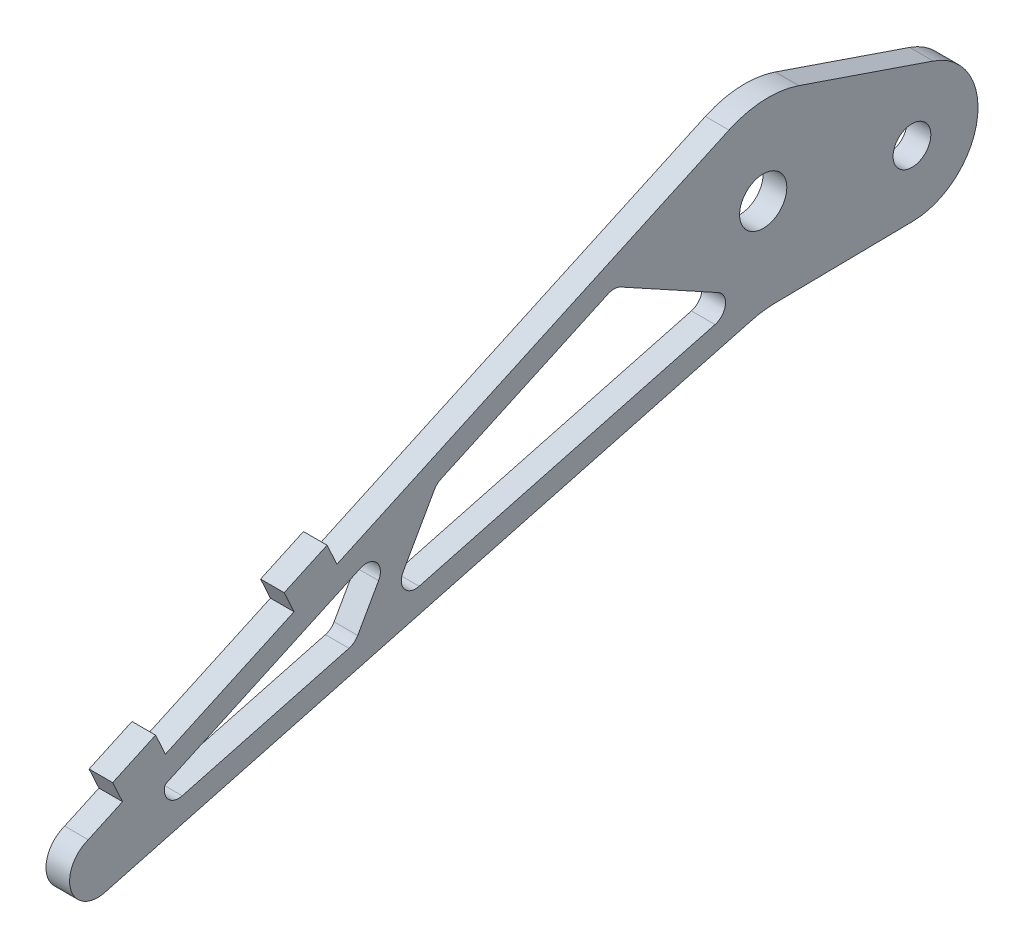
SolidWorks part; units mm, degrees
ref_plane "Front Plane" through (0, 0, 0) normal (1, 0, 0) x (0, 1, 0)
ref_plane "Top Plane" through (0, 0, 0) normal (0, 0, 1) x (0, 1, 0)
ref_plane "Right Plane" through (0, 0, 0) normal (0, 1, 0) x (-1, 0, 0)
sketch "Sketch1" plane through (0, 0, 0) normal (1, 0, 0) x (0, 1, 0)
  line L0 (0, 0) -> (5.5567, 31.5138) construction
  line L1 (5.5567, 31.5138) -> (-45.7463, 172.4677) construction
  line L2 (0, 0) -> (50000, 0) construction
  line L3 (5.5567, 31.5138) -> (-14.4433, 31.5138) construction
  line L4 (-13.9986, -0.1963) -> (-14.4433, 31.5138)
  line L5 (-14.4433, 31.5138) -> (-51.3844, 170.4156)
  line L6 (-45.7463, 172.4677) -> (-51.3844, 170.4156) construction
  line L7 (5.5567, 31.5138) -> (25.5567, 31.5138) construction
  line L8 (13.2486, -4.5247) -> (25.5567, 31.5138)
  line L9 (-45.7463, 172.4677) -> (-40.1081, 174.5199) construction
  line L10 (-40.1081, 174.5199) -> (25.5567, 31.5138)
  line L11 (0, 0) -> (-45.7463, 172.4677) construction
  line L12 (-30.4865, 111.2917) -> (-10.0592, 34.4834)
  line L13 (5.6, 62.9939) -> (-11.7181, 100.7094)
  line L14 (-11.7181, 100.7094) -> (-30.4865, 111.2917)
  line L17 (-15.2745, 108.4546) -> (-38.215, 158.4149)
  line L18 (-38.215, 158.4149) -> (-44.1163, 162.5408)
  line L19 (-44.1163, 162.5408) -> (-32.2824, 118.0442)
  line L20 (-32.2824, 118.0442) -> (-15.2745, 108.4546)
  line L21 (-10.0592, 34.4834) -> (5.6, 62.9939)
  line L22 (-17.9919, 126.3548) -> (-34.6834, 162.7058)
  line L23 (-34.6834, 162.7058) -> (-30.1395, 164.7922) construction
  line L24 (-17.9919, 126.3548) -> (-13.456, 128.4586) construction
  line L25 (-28.0531, 160.2484) -> (-32.226, 169.3361)
  line L26 (-11.3696, 123.9147) -> (-15.5425, 133.0025)
  line L27 (-32.226, 169.3361) -> (-36.7698, 167.2497)
  line L28 (-28.0531, 160.2484) -> (-32.597, 158.1619)
  line L29 (-15.5425, 133.0025) -> (-20.0863, 130.916)
  line L30 (-11.3696, 123.9147) -> (-15.9134, 121.8283)
  circle A0 centre (0, 0) radius 4
  circle A1 centre (5.5567, 31.5138) radius 5
  arc A2 (-13.9986, -0.1963) -> (13.2486, -4.5247) centre (0, 0) ccw
  arc A3 (-51.3844, 170.4156) -> (-40.1081, 174.5199) centre (-45.7463, 172.4677) cw
  arc A4 (14, 0) -> (2.4311, 13.7873) centre (0, 0) ccw construction
  arc A5 (2.4311, 13.7873) -> (-13.9986, -0.1963) centre (0, 0) ccw construction
  circle A6 centre (0, 0) radius 14 construction
  arc A7 (13.2486, -4.5247) -> (14, 0) centre (0, 0) ccw construction
  point P14 (14, 0)
  point P29 (-26.3376, 144.5303)
  point P35 (-30.1395, 164.7922)
  point P39 (-13.456, 128.4586)
  dimension "D6" = 8
  dimension "D7" = 10
  dimension "D11" = 5
  dimension "D1" = 100
  dimension "D2" = 32
  dimension "D3" = 20
  dimension "D4" = 70
  dimension "D5" = 150
  dimension "D9" = 6
  dimension "D10" = 20
  dimension "D12" = 0
  dimension "D13" = 5
  dimension "D14" = 5
  dimension "D15" = 5
  dimension "D16" = 19.525
  dimension "D17" = 5
  dimension "D18" = 40
  dimension "D19" = 5
  dimension "D20" = 10
  dimension "D21" = 33
  dimension "D8" = 10
extrude "Boss-Extrude1" add sketch "Sketch1" against normal blind 5 contours A3 L5 L4 A2 L8 L10 L22 A1 A0 L21 L12 L14 L13 L20 L19 L18 L17 | L30 L26 L29 L10 | L28 L25 L27 L10 region at (0, -12.147, 15.6879) region at (0, -15.728, 127.4154) region at (0, -32.4115, 163.749)
fillet "Fillet3" radius 20 2 edges at (-2.5, -14.4433, 31.5138) (-2.5, 25.5567, 31.5138)
ref_plane "Plane1" through (15, 0, 0) normal (1, 0, 0) x (0, 1, 0)
fillet "Fillet10" radius 3 8 edges at (-2.5, -38.215, 158.4149) (-2.5, -32.2824, 118.0442) (-2.5, -30.4865, 111.2917) (-2.5, -11.7181, 100.7094) (-2.5, -10.0592, 34.4834) (-2.5, 5.6, 62.9939) (-2.5, -15.2745, 108.4546) (-2.5, -44.1163, 162.5408)
